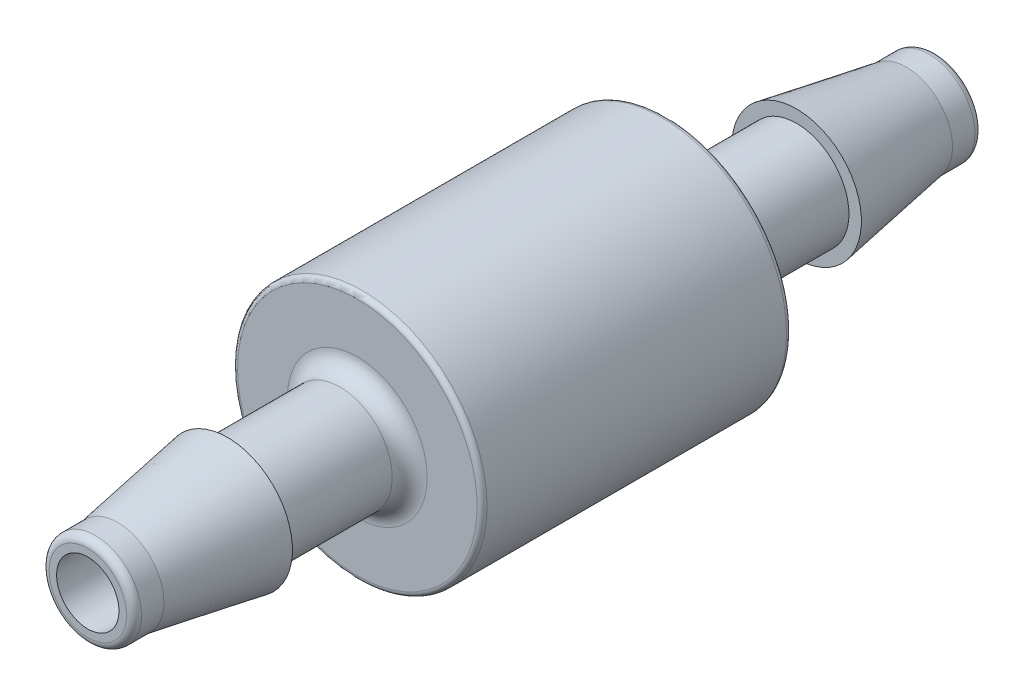
SolidWorks part; units mm, degrees
ref_plane "Front Plane" through (0, 0, 0) normal (0, 0, 1) x (1, 0, 0)
ref_plane "Top Plane" through (0, 0, 0) normal (0, 1, 0) x (1, 0, 0)
ref_plane "Right Plane" through (0, 0, 0) normal (1, 0, 0) x (0, 0, -1)
sketch "Sketch1" plane through (0, 0, 0) normal (1, 0, 0) x (0, 0, -1)
  line L0 (-21.59, 0) -> (21.59, 0) construction
  line L1 (21.59, 6.35) -> (21.59, -6.35) construction
  line L2 (-21.59, 1.5875) -> (-21.59, -1.5875) construction
  line L4 (-21.59, 2.3813) -> (-21.59, -2.3813) construction
  line L6 (21.59, -2.3813) -> (21.59, 2.3812) construction
  line L8 (-21.59, 6.35) -> (-21.59, -6.35) construction
  point P20 (-7.874, 0)
  point P21 (7.874, 0)
  point P26 (21.59, 0)
  point P27 (21.59, 2.3812)
  point P28 (21.59, -2.3813)
  point P29 (-21.59, 2.3813)
  point P30 (-21.59, -2.3813)
  dimension "OD" = 12.7
  dimension "End to End Length" = 43.18
  dimension "ID" = 3.175
  dimension "L1" = 13.716
  dimension "L2" = 15.748
  dimension "L3" = 13.716
  dimension "For Inlet Tube ID" = 4.7625
  dimension "For Outlet Tube ID" = 4.7625
sketch "Sketch2" plane through (0, 0, 0) normal (1, 0, 0) x (0, 0, -1)
  line L0 (21.59, 0) -> (-21.59, 0) construction
  line L1 (21.59, 6.35) -> (21.59, -6.35) construction
  line L2 (-21.59, 1.5875) -> (-21.59, -1.5875) construction
  line L3 (-21.59, 1.5875) -> (-21.59, 1.9685)
  line L4 (14.478, 2.667) -> (8.763, 2.667)
  line L5 (21.209, 2.3495) -> (20.066, 2.3495)
  line L6 (7.874, 3.556) -> (7.874, 6.096)
  line L7 (21.59, 1.5875) -> (21.59, 1.9685)
  line L8 (-7.874, 3.556) -> (-7.874, 6.096)
  line L9 (-7.62, 6.35) -> (7.62, 6.35)
  line L10 (14.478, 3.302) -> (14.478, 2.667)
  line L11 (20.066, 2.3495) -> (14.478, 3.302)
  line L14 (0, 0) -> (0, 6.35) construction
  line L15 (-21.209, 2.3495) -> (-20.066, 2.3495)
  line L17 (-20.066, 2.3495) -> (-14.478, 3.302)
  line L18 (-14.478, 3.302) -> (-14.478, 2.667)
  line L19 (-14.478, 2.667) -> (-8.763, 2.667)
  line L24 (-21.59, 1.5875) -> (21.59, 1.5875)
  arc A0 (7.874, 6.096) -> (7.62, 6.35) centre (7.62, 6.096) ccw
  arc A1 (-7.874, 6.096) -> (-7.62, 6.35) centre (-7.62, 6.096) cw
  arc A2 (-21.209, 2.3495) -> (-21.59, 1.9685) centre (-21.209, 1.9685) ccw
  arc A3 (21.209, 2.3495) -> (21.59, 1.9685) centre (21.209, 1.9685) cw
  arc A4 (-8.763, 2.667) -> (-7.874, 3.556) centre (-8.763, 3.556) ccw
  arc A5 (8.763, 2.667) -> (7.874, 3.556) centre (8.763, 3.556) cw
  dimension "D3" = 6.604
  dimension "D4" = 5.588
  dimension "D5" = 5.334
  dimension "R1" = 0.254
  dimension "R2" = 0.381
  dimension "R3" = 0.889
  dimension "D1" = 4.699
  dimension "D2" = 1.524
revolve "Revolve1" add sketch "Sketch2" angle 360 mid plane about L0
sketch "SketchX" plane through (0, 0, 0) normal (1, 0, 0) x (0, 0, -1)
  line L10 (21.59, 1.5875) -> (-21.59, 1.5875) construction
  line L12 (-21.59, -1.5875) -> (21.59, -1.5875) construction
  line L13 (21.59, 1.5875) -> (-21.59, 1.5875)
  line L14 (-21.59, -1.5875) -> (21.59, -1.5875)
ref_point "Point1"
ref_point "Point2"
ref_axis "Axis1" through (0, 0, 18.1826) along (0, 0, -1)
